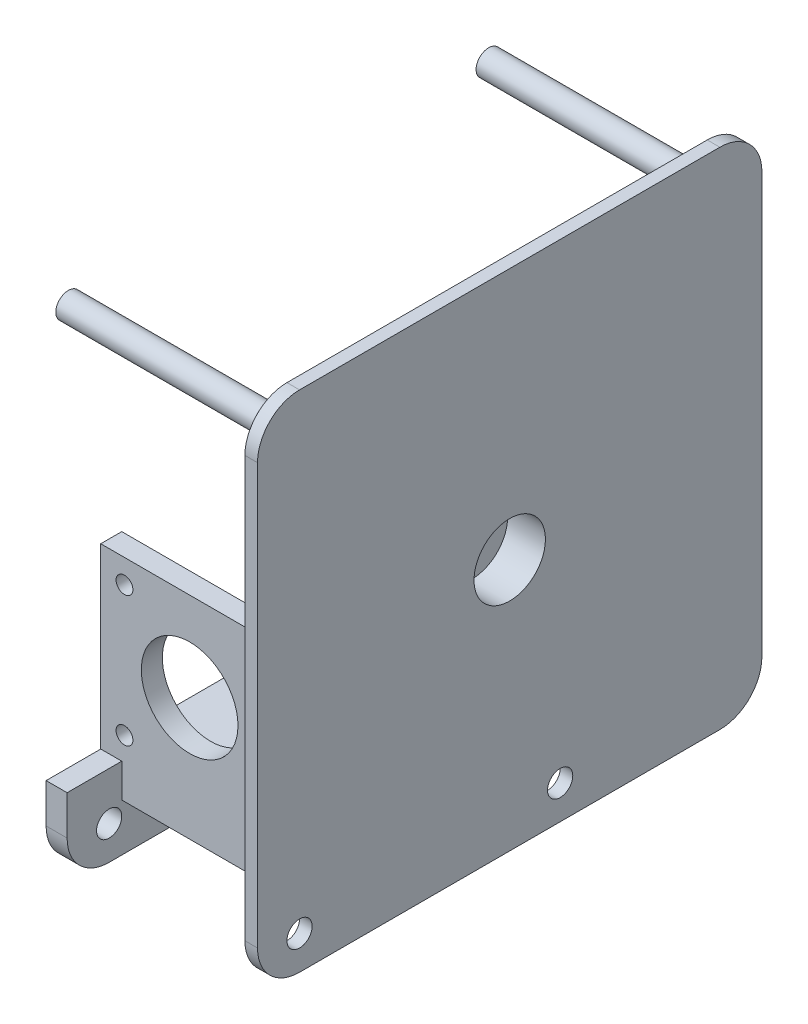
SolidWorks part; units mm, degrees
ref_plane "Alzado" through (0, 0, 0) normal (0, 0, 1) x (1, 0, 0)
ref_plane "Planta" through (0, 0, 0) normal (0, 1, 0) x (1, 0, 0)
ref_plane "Vista lateral" through (0, 0, 0) normal (1, 0, 0) x (0, 0, -1)
sketch "Croquis1" plane through (0, 0, 0) normal (0, 1, 0) x (1, 0, 0)
  circle A0 centre (0, 0) radius 10
  dimension "D1" = 20
extrude "Saliente-Extruir1" add sketch "Croquis1" along normal blind 10
sketch "Croquis3" plane through (0, 0, 0) normal (0, -1, 0) x (1, 0, 0)
  line L1 (62, 15) -> (-77, 15)
  line L2 (62, 15) -> (62, -45)
  line L3 (62, -45) -> (-77, -45)
  line L4 (-77, 15) -> (-77, -45)
  dimension "D1" = 60
  dimension "D2" = 139
  dimension "D3" = 45
  dimension "D4" = 62
extrude "Saliente-Extruir2" add sketch "Croquis3" along normal blind 8
sketch "Croquis2" plane through (0, 10, 0) normal (0, 1, 0) x (1, 0, 0)
  line L0 (2.2361, 2) -> (-2.2361, 2)
  arc A0 (-2.2361, 2) -> (2.2361, 2) centre (0, 0) ccw
  dimension "D1" = 6
  dimension "D2" = 2
extrude "Cortar-Extruir1" cut sketch "Croquis2" against normal up to next
fillet "Redondeo1" radius 3 1 edges at (0, 0, 10) type face fillet first side face at (0, 10, 10) second side face at (0, 0, 10)
sketch "Croquis4" plane through (0, 0, 15) normal (0, 0, 1) x (1, 0, 0)
  line L4 (62, 0) -> (-77, 0)
  line L5 (-77, 0) -> (-77, -8)
  line L6 (-77, -8) -> (62, -8)
  line L7 (62, -8) -> (62, 0)
  line L8 (62, 0) -> (-77, 0)
  line L9 (-77, 0) -> (-77, -8)
  line L10 (-77, -8) -> (62, -8)
  line L11 (62, -8) -> (62, 0)
  dimension "D1" = 0
extrude "Saliente-Extruir3" add sketch "Croquis4" along normal blind 40
sketch "Croquis6" plane through (0, 0, 0) normal (0, 1, 0) x (1, 0, 0)
  line L5 (-46.7, 12.5) -> (-29.7, 12.5)
  line L6 (-46.7, 12.5) -> (-46.7, -12.5)
  line L7 (-46.7, -12.5) -> (-29.7, -12.5)
  line L8 (-29.7, 12.5) -> (-29.7, -12.5)
  line L9 (14.7, 12.5) -> (31.7, 12.5)
  line L10 (14.7, 12.5) -> (14.7, -12.5)
  line L11 (14.7, -12.5) -> (31.7, -12.5)
  line L12 (31.7, 12.5) -> (31.7, -12.5)
  dimension "D1" = 25
  dimension "D2" = 12.5
  dimension "D3" = 17
  dimension "D4" = 17
  dimension "D5" = 25
  dimension "D7" = 14.7
  dimension "D8" = 29.7
extrude "Saliente-Extruir4" add sketch "Croquis6" along normal blind 52.65
sketch "Croquis7" plane through (31.7, 0, 0) normal (1, 0, 0) x (0, 0, -1)
  line L2 (-12.5, 52.65) -> (-12.5, 0) construction
  line L3 (-12.5, 52.65) -> (12.5, 52.65) construction
  circle A0 centre (0, 40.65) radius 3
  dimension "D1" = 6
  dimension "D2" = 12.5
  dimension "D3" = 12
extrude "Cortar-Extruir2" cut sketch "Croquis7" against normal blind 119
sketch "Croquis8" plane through (31.7, 0, 0) normal (1, 0, 0) x (0, 0, -1)
  circle A0 centre (0, 40.65) radius 8.5
  dimension "D1" = 17
extrude "Cortar-Extruir3" cut sketch "Croquis8" against normal blind 6
sketch "Croquis9" plane through (14.7, 0, 0) normal (-1, 0, 0) x (0, 0, 1)
  circle A0 centre (0, 40.65) radius 8.5
  dimension "D1" = 17
extrude "Cortar-Extruir4" cut sketch "Croquis9" against normal blind 6
sketch "Croquis10" plane through (-29.7, 0, 0) normal (1, 0, 0) x (0, 0, -1)
  circle A0 centre (0, 40.65) radius 8.5
  dimension "D1" = 17
extrude "Cortar-Extruir5" cut sketch "Croquis10" against normal blind 6
sketch "Croquis11" plane through (-46.7, 0, 0) normal (-1, 0, 0) x (0, 0, 1)
  circle A0 centre (0, 40.65) radius 8.5
  dimension "D1" = 17
extrude "Cortar-Extruir6" cut sketch "Croquis11" against normal blind 6
sketch "Croquis12" plane through (0, 0, -45) normal (0, 0, -1) x (-1, 0, 0)
  line L0 (77, 0) -> (-62, 0) construction
  circle A0 centre (0, 6) radius 2
  dimension "D1" = 4
  dimension "D2" = 6
extrude "Cortar-Extruir7" cut sketch "Croquis12" against normal blind 79
sketch "Croquis13" plane through (0, 0, 0) normal (0, 1, 0) x (1, 0, 0)
  line L0 (62, 45) -> (62, -55) construction
  line L1 (62, -47) -> (19.7, -47)
  line L2 (62, -47) -> (62, -42)
  line L3 (62, -42) -> (19.7, -42)
  line L4 (19.7, -47) -> (19.7, -42)
  line L5 (-77, -55) -> (-77, 45) construction
  line L6 (-77, -47) -> (-34.7, -47)
  line L7 (-77, -47) -> (-77, -42)
  line L8 (-77, -42) -> (-34.7, -42)
  line L9 (-34.7, -47) -> (-34.7, -42)
  line L10 (62, -55) -> (-77, -55) construction
  dimension "D1" = 5
  dimension "D2" = 42.3
  dimension "D3" = 42.3
  dimension "D4" = 8
  dimension "D5" = 8
extrude "Saliente-Extruir5" add sketch "Croquis13" along normal blind 42.3
sketch "Croquis14" plane through (0, 0, 47) normal (0, 0, 1) x (1, 0, 0)
  line L0 (40.85, 42.3) -> (40.85, 17.188) construction
  line L1 (19.7, 42.3) -> (62, 42.3) construction
  line L2 (19.7, 21.15) -> (42.4958, 21.15) construction
  line L3 (19.7, 42.3) -> (19.7, 0) construction
  line L4 (-55.85, 42.3) -> (-55.85, 9.9453) construction
  line L5 (-77, 42.3) -> (-34.7, 42.3) construction
  line L6 (-77, 21.15) -> (-47.6717, 21.15) construction
  line L7 (-77, 42.3) -> (-77, 0) construction
  line L8 (62, 42.3) -> (62, 0) construction
  circle A0 centre (40.85, 21.15) radius 11.5
  circle A1 centre (25.35, 36.65) radius 2
  circle A2 centre (56.35, 36.65) radius 2
  circle A3 centre (56.35, 5.65) radius 2
  circle A4 centre (25.35, 5.65) radius 2
  circle A5 centre (-55.85, 21.15) radius 11.5
  circle A6 centre (-40.35, 36.65) radius 2
  circle A7 centre (-71.35, 36.65) radius 2
  circle A8 centre (-40.35, 5.65) radius 2
  circle A9 centre (-71.35, 5.65) radius 2
  dimension "D1" = 23
  dimension "D2" = 23
  dimension "D9" = 4
  dimension "D10" = 4
  dimension "D11" = 4
  dimension "D12" = 4
  dimension "D13" = 4
  dimension "D14" = 4
  dimension "D15" = 4
  dimension "D16" = 4
  dimension "D3" = 31
  dimension "D4" = 31
  dimension "D5" = 31
  dimension "D6" = 5.65
  dimension "D7" = 5.65
  dimension "D8" = 5.65
extrude "Cortar-Extruir8" cut sketch "Croquis14" against normal up to next
fillet "Redondeo2" radius 10 1 edges at (-46.7, 0, 0) type face fillet first side face at (-46.7, 40.65, 8.5) second side face at (0, 0, 13)
fillet "Redondeo3" radius 10 1 edges at (-43.2, 0, -12.5) type face fillet first side face at (-41.4858, 22.6458, -12.5) second side face at (0, 0, 13)
fillet "Redondeo4" radius 10 1 edges at (-29.7, 0, -5) type face fillet first side face at (-29.7, 40.65, -8.5) second side face at (0, 0, 13)
fillet "Redondeo5" radius 10 1 edges at (23.2, 0, -12.5) type face fillet first side face at (23.2, 26.325, -12.5) second side face at (0, 0, 13)
fillet "Redondeo6" radius 10 1 edges at (31.7, 0, -5) type face fillet first side face at (31.7, 40.65, -8.5) second side face at (0, 0, 13)
fillet "Redondeo7" radius 3 1 edges at (14.7, 0, -5) type face fillet first side face at (14.7, 40.65, 8.5) second side face at (0, 0, 13)
sketch "Croquis20" plane through (-34.7, 0, 0) normal (1, 0, 0) x (0, 0, -1)
  line L0 (-12.5, 52.65) -> (-12.5, 10) construction
  line L1 (-47, 0) -> (-12.5, 0)
  line L2 (-47, 0) -> (-47, 42.3)
  line L3 (-47, 42.3) -> (-12.5, 42.3)
  line L4 (-12.5, 0) -> (-12.5, 42.3)
extrude "Saliente-Extruir8" add sketch "Croquis20" along normal blind 5
sketch "Croquis21" plane through (19.7, 0, 0) normal (-1, 0, 0) x (0, 0, 1)
  line L1 (47, 0) -> (12.5, 0)
  line L2 (47, 0) -> (47, 42.3)
  line L3 (47, 42.3) -> (12.5, 42.3)
  line L4 (12.5, 0) -> (12.5, 42.3)
extrude "Saliente-Extruir9" add sketch "Croquis21" along normal blind 5
fillet "Redondeo10" radius 10 1 edges at (-77, -4, -45) type face fillet first side face at (-77, 8.575, 24.75) second side face at (-7.5, -4, -45)
fillet "Redondeo11" radius 10 1 edges at (62, -4, -45) type face fillet first side face at (62, 8.575, 24.75) second side face at (-2.5, -4, -45)
sketch "Croquis18" plane through (0, 10, 0) normal (0, 1, 0) x (1, 0, 0)
  line L1 (-0.5, -3.57) -> (0.5, -3.57)
  line L2 (-0.5, -3.57) -> (-0.5, -8.57)
  line L3 (-0.5, -8.57) -> (0.5, -8.57)
  line L4 (0.5, -3.57) -> (0.5, -8.57)
  dimension "D1" = 0.5
  dimension "D2" = 1
  dimension "D3" = 5
extrude "Cortar-Extruir10" cut sketch "Croquis18" against normal blind 1
sketch "Croquis22" plane through (0, 52.65, 0) normal (0, 1, 0) x (1, 0, 0)
  line L1 (-29.7, -47) -> (67.8995, -47)
  line L2 (-29.7, -47) -> (-29.7, 53.7702)
  line L3 (-29.7, 53.7702) -> (67.8995, 53.7702)
  line L4 (67.8995, -47) -> (67.8995, 53.7702)
extrude "Cortar-Extruir11" cut sketch "Croquis22" against normal blind 72
sketch "Croquis23" plane through (0, 0, 0) normal (0, 1, 0) x (1, 0, 0)
  line L1 (-29.7, -47) -> (67.4832, -47)
  line L2 (-29.7, -47) -> (-29.7, -64.8932)
  line L3 (-29.7, -64.8932) -> (67.4832, -64.8932)
  line L4 (67.4832, -47) -> (67.4832, -64.8932)
extrude "Cortar-Extruir12" cut sketch "Croquis23" against normal blind 27
sketch "Croquis24" plane through (0, 52.65, 0) normal (0, 1, 0) x (1, 0, 0)
  line L1 (-77, -55) -> (-29.7, -55)
  line L2 (-77, -55) -> (-77, -47)
  line L3 (-77, -47) -> (-29.7, -47)
  line L4 (-29.7, -55) -> (-29.7, -47)
  line L5 (-29.7, 12.5) -> (-81.1634, 12.5)
  line L6 (-29.7, 12.5) -> (-29.7, 55.8264)
  line L7 (-29.7, 55.8264) -> (-81.1634, 55.8264)
  line L8 (-81.1634, 12.5) -> (-81.1634, 55.8264)
extrude "Cortar-Extruir13" cut sketch "Croquis24" against normal blind 62
sketch "Croquis25" plane through (0, 0, 47) normal (0, 0, 1) x (1, 0, 0)
  circle A0 centre (-40.35, 5.65) radius 2
  circle A1 centre (-40.35, 36.65) radius 2
extrude "Cortar-Extruir14" cut sketch "Croquis25" against normal blind 62
sketch "Croquis26" plane through (-29.7, 0, 0) normal (1, 0, 0) x (0, 0, -1)
  line L1 (-50, -19.35) -> (50, -19.35)
  line L2 (-60, -9.35) -> (-60, 90.65)
  line L3 (-50, 100.65) -> (50, 100.65)
  line L4 (60, -9.35) -> (60, 90.65)
  circle A0 centre (0, 40.65) radius 8.5 construction
  circle A1 centre (0, 40.65) radius 8.5 construction
  arc A2 (-50, 100.65) -> (-60, 90.65) centre (-50, 90.65) ccw
  arc A3 (-60, -9.35) -> (-50, -19.35) centre (-50, -9.35) ccw
  arc A4 (60, -9.35) -> (50, -19.35) centre (50, -9.35) cw
  arc A5 (50, 100.65) -> (60, 90.65) centre (50, 90.65) cw
  circle A6 centre (0, 40.65) radius 8.5
  point P10 (-60, 100.65)
  point P13 (-60, -19.35)
  point P18 (60, 100.65)
  dimension "D3" = 60
  dimension "D4" = 60
  dimension "D5" = 10
  dimension "D1" = 120
  dimension "D2" = 120
extrude "Saliente-Extruir10" add sketch "Croquis26" along normal blind 3
sketch "Croquis27" plane through (-77, 0, 0) normal (-1, 0, 0) x (0, 0, 1)
  line L0 (60, 90.65) -> (60, -9.35) construction
  line L1 (-28, 0) -> (60, 0)
  line L2 (-28, 0) -> (-28, -19.35)
  line L3 (-28, -19.35) -> (50, -19.35)
  line L4 (60, 0) -> (60, -9.35)
  line L5 (50, -19.35) -> (-50, -19.35) construction
  arc A0 (50, -19.35) -> (60, -9.35) centre (50, -9.35) ccw
  dimension "D2" = 10
  dimension "D1" = 88
extrude "Saliente-Extruir11" add sketch "Croquis27" against normal blind 5
sketch "Croquis28" plane through (-29.7, 0, 0) normal (-1, 0, 0) x (0, 0, 1)
  line L1 (50, -19.35) -> (-50, -19.35) construction
  line L2 (60, 90.65) -> (60, -9.35) construction
  circle A0 centre (-12, -11.35) radius 3
  circle A1 centre (50, -11.35) radius 3
  dimension "D4" = 6
  dimension "D5" = 6
  dimension "D1" = 62
  dimension "D2" = 8
  dimension "D3" = 10
extrude "Cortar-Extruir15" cut sketch "Croquis28" against normal mid plane 106
sketch "Croquis29" plane through (-29.7, 0, 0) normal (-1, 0, 0) x (0, 0, 1)
  line L0 (-60, -9.35) -> (-60, 90.65) construction
  line L1 (50, -19.35) -> (-50, -19.35) construction
  line L2 (-50, 100.65) -> (50, 100.65) construction
  line L3 (60, 90.65) -> (60, -9.35) construction
  circle A0 centre (-50, 90.65) radius 3
  circle A1 centre (50, 90.65) radius 3
  circle A2 centre (-50, -9.35) radius 3
  dimension "D7" = 6
  dimension "D8" = 6
  dimension "D9" = 6
  dimension "D1" = 10
  dimension "D2" = 10
  dimension "D3" = 10
  dimension "D4" = 10
  dimension "D5" = 10
  dimension "D6" = 10
extrude "Saliente-Extruir12" add sketch "Croquis29" along normal blind 52
fillet "Redondeo12" radius 5 1 edges at (-29.7, -9.35, -53) type face fillet first side face at (-81.7, -9.35, -47) second side face at (-29.7, -9.35, -53)
fillet "Redondeo13" radius 5 1 edges at (-29.7, 90.65, -53) type face fillet first side face at (-81.7, 90.65, -47) second side face at (-29.7, -9.35, -58)
fillet "Redondeo14" radius 5 1 edges at (-29.7, 90.65, 47) type face fillet first side face at (-81.7, 90.65, 53) second side face at (-29.7, 90.65, -58)
